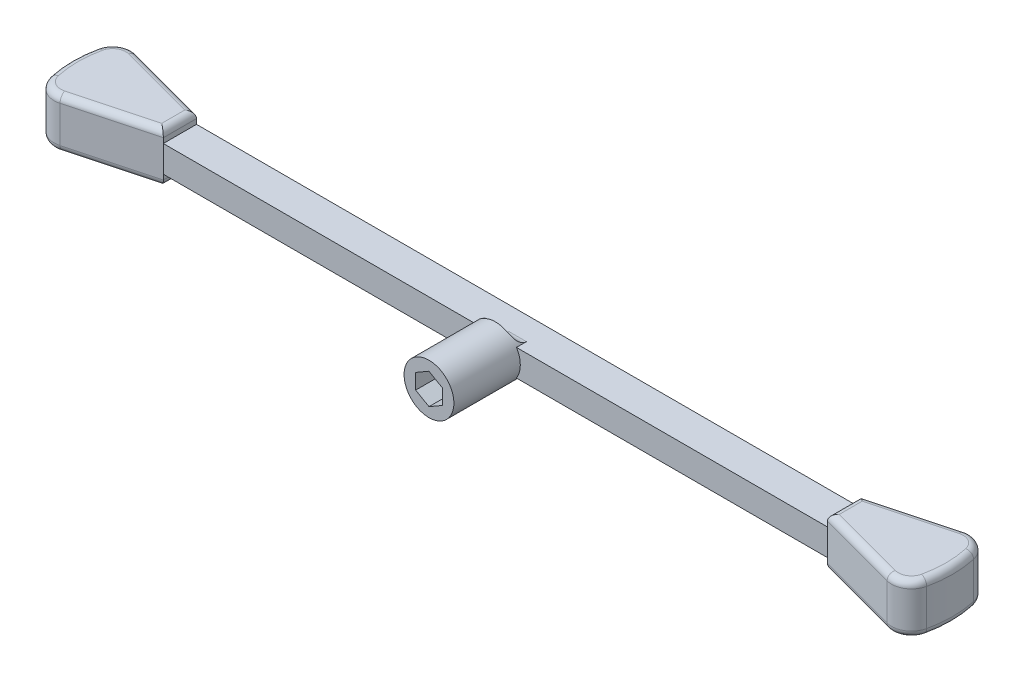
SolidWorks part; units mm, degrees
ref_plane "前视基准面" through (0, 0, 0) normal (0, 0, 1) x (1, 0, 0)
ref_plane "上视基准面" through (0, 0, 0) normal (0, 1, 0) x (1, 0, 0)
ref_plane "右视基准面" through (0, 0, 0) normal (1, 0, 0) x (0, 0, -1)
sketch "草图1" plane through (0, 0, 0) normal (0, 0, 1) x (1, 0, 0)
  line L1 (0, -4.6188) -> (4, -2.3094)
  line L2 (4, -2.3094) -> (4, 2.3094)
  line L3 (4, 2.3094) -> (0, 4.6188)
  line L4 (0, 4.6188) -> (-4, 2.3094)
  line L5 (-4, 2.3094) -> (-4, -2.3094)
  line L6 (-4, -2.3094) -> (0, -4.6188)
  circle A0 centre (0, 0) radius 7.5
  circle A1 centre (0, 0) radius 4 construction
  dimension "D1" = 15
  dimension "D2" = 8
extrude "凸台-拉伸1" add sketch "草图1" along normal blind 20
sketch "草图2" plane through (0, 0, 0) normal (0, 0, -1) x (-1, 0, 0)
  line L0 (-43.4127, 0) -> (46.9816, 0) construction
  line L1 (0, 46.224) -> (0, -56.1658) construction
  line L2 (-100, 4) -> (100, 4)
  line L3 (-100, 4) -> (-100, -4)
  line L4 (-100, -4) -> (100, -4)
  line L5 (100, 4) -> (100, -4)
  dimension "D1" = 8
  dimension "D2" = 200
extrude "凸台-拉伸2" add sketch "草图2" along normal blind 10
ref_plane "基准面1" through (0, 0, 0) normal (0, 1, 0) x (1, 0, 0)
sketch "草图3" plane through (0, 0, 0) normal (0, 1, 0) x (1, 0, 0)
  line L0 (-100, 10) -> (-130, 18.0385)
  line L1 (-126.7286, 5) -> (143.7462, 5) construction
  line L2 (-100, 10) -> (100, 10) construction
  line L3 (-100, 0) -> (-6.3443, 0) construction
  line L4 (-130, 23.9533) -> (-130, -6.5984) construction
  line L5 (-100, 10) -> (-100, 0) construction
  line L6 (-100, 0) -> (-130, -8.0385)
  line L7 (-100, 10) -> (-100, 0)
  line L8 (0, 59.6597) -> (0, -60.1187) construction
  line L9 (100, 10) -> (100, 0)
  line L10 (100, 0) -> (130, -8.0385)
  line L11 (100, 10) -> (130, 18.0385)
  arc A1 (-130, 18.0385) -> (-130, -8.0385) centre (-100, 5) ccw
  arc A2 (130, 18.0385) -> (130, -8.0385) centre (100, 5) cw
  dimension "D1" = 30
  dimension "D2" = 15
extrude "凸台-拉伸3" add sketch "草图3" along normal mid plane 15
fillet "圆角2" radius 6 4 edges at (130, 0, -18.0385) (130, 0, 8.0385) (-130, 0, -18.0385) (-130, 0, 8.0385)
fillet "圆角3" radius 2 24 edges at (100, -7.5, -5) (112.263, -7.5, 3.2859) (129.192, -7.5, 5.9053) (132.7109, -7.5, -5) (129.192, -7.5, -15.9053) (112.263, -7.5, -13.2859) (129.192, 7.5, 5.9053) (112.263, 7.5, 3.2859) (100, 7.5, -5) (112.263, 7.5, -13.2859) (129.192, 7.5, -15.9053) (132.7109, 7.5, -5) (-100, 7.5, -5) (-112.263, 7.5, 3.2859) (-129.192, 7.5, 5.9053) (-132.7109, 7.5, -5) (-129.192, 7.5, -15.9053) (-112.263, 7.5, -13.2859) (-129.192, -7.5, 5.9053) (-112.263, -7.5, 3.2859) (-100, -7.5, -5) (-112.263, -7.5, -13.2859) (-129.192, -7.5, -15.9053) (-132.7109, -7.5, -5)
fillet "圆角4" radius 3 4 edges at (3.708, -4, 0) (-3.708, -4, 0) (-3.708, 4, 0) (3.708, 4, 0)
